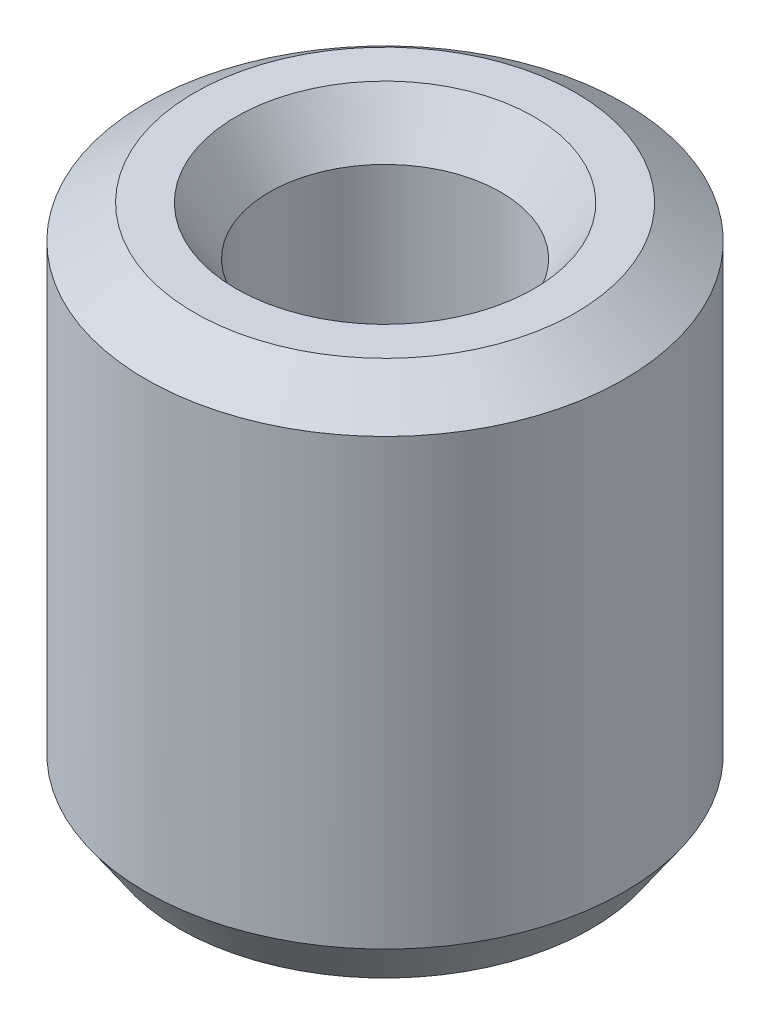
SolidWorks part; units mm, degrees
ref_plane "Front Plane" through (0, 0, 0) normal (0, 0, 1) x (1, 0, 0)
ref_plane "Top Plane" through (0, 0, 0) normal (0, 1, 0) x (1, 0, 0)
ref_plane "Right Plane" through (0, 0, 0) normal (1, 0, 0) x (0, 0, -1)
sketch "Sketch1" plane through (0, 0, 0) normal (0, 1, 0) x (1, 0, 0)
  circle A0 centre (0, 0) radius 10
  dimension "SLEEVE_OD" = 20
extrude "Boss-Extrude1" add sketch "Sketch1" along normal blind 21.9879
sketch "Sketch2" plane through (0, 0, 0) normal (0, 1, 0) x (1, 0, 0)
  circle A0 centre (0, 0) radius 4.8373
  dimension "BORE_D" = 9.6746
extrude "Cut-Extrude1" cut sketch "Sketch2" along normal through all
chamfer "Chamfer1" distance 1.3929 angle 55.561 4 edges at (0, 21.9879, 4.8373) (0, 0, 4.8373) (0, 0, 10) (0, 21.9879, 10) first distance on face at (0, 21.9879, 4.8373) first distance on face at (0, 0, 4.8373) first distance on face at (0, 21.9879, 10)
